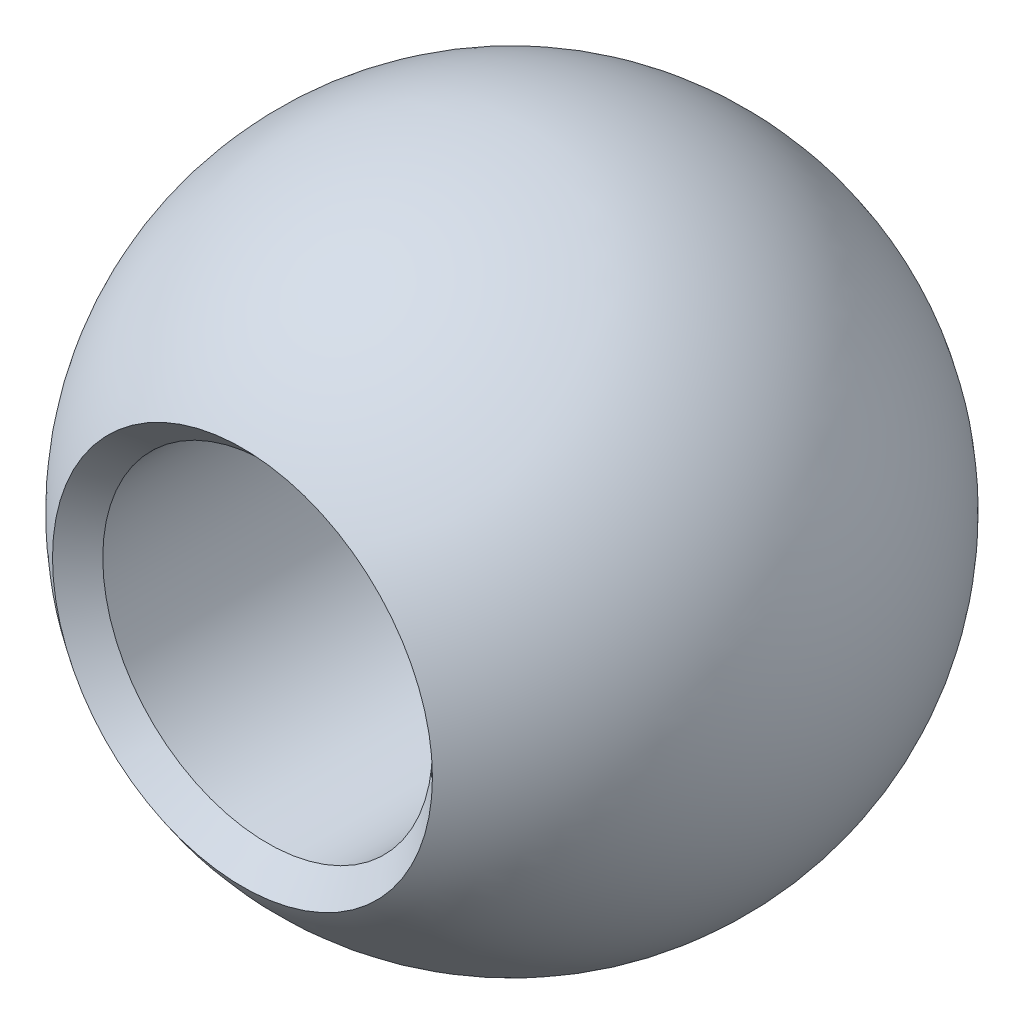
SolidWorks part; units mm, degrees
ref_plane "Спереди" through (0, 0, 0) normal (0, 0, 1) x (1, 0, 0)
ref_plane "Сверху" through (0, 0, 0) normal (0, 1, 0) x (1, 0, 0)
ref_plane "Справа" through (0, 0, 0) normal (1, 0, 0) x (0, 0, -1)
sketch "Эскиз1" plane through (0, 0, 0) normal (0, 0, 1) x (1, 0, 0)
  line L0 (0, 8) -> (0, -8) construction
  line L1 (0, 8) -> (0, -8)
  arc A0 (0, 8) -> (0, -8) centre (0, 0) cw
  dimension "D1" = 8
revolve "Повернуть1" add sketch "Эскиз1" angle 360 about L0
sketch "Эскиз2" plane through (0, 0, 0) normal (0, 0, 1) x (1, 0, 0)
  circle A0 centre (0, 0) radius 4
  dimension "D1" = 8
extrude "Вырез-Вытянуть1" cut sketch "Эскиз2" against normal through all and the other way through all
chamfer "Фаска1" distance 1 angle 45 2 edges at (-4, 0, 6.9282) (4, 0, -6.9282) first distance on face at (4, 0, -6.9282)
